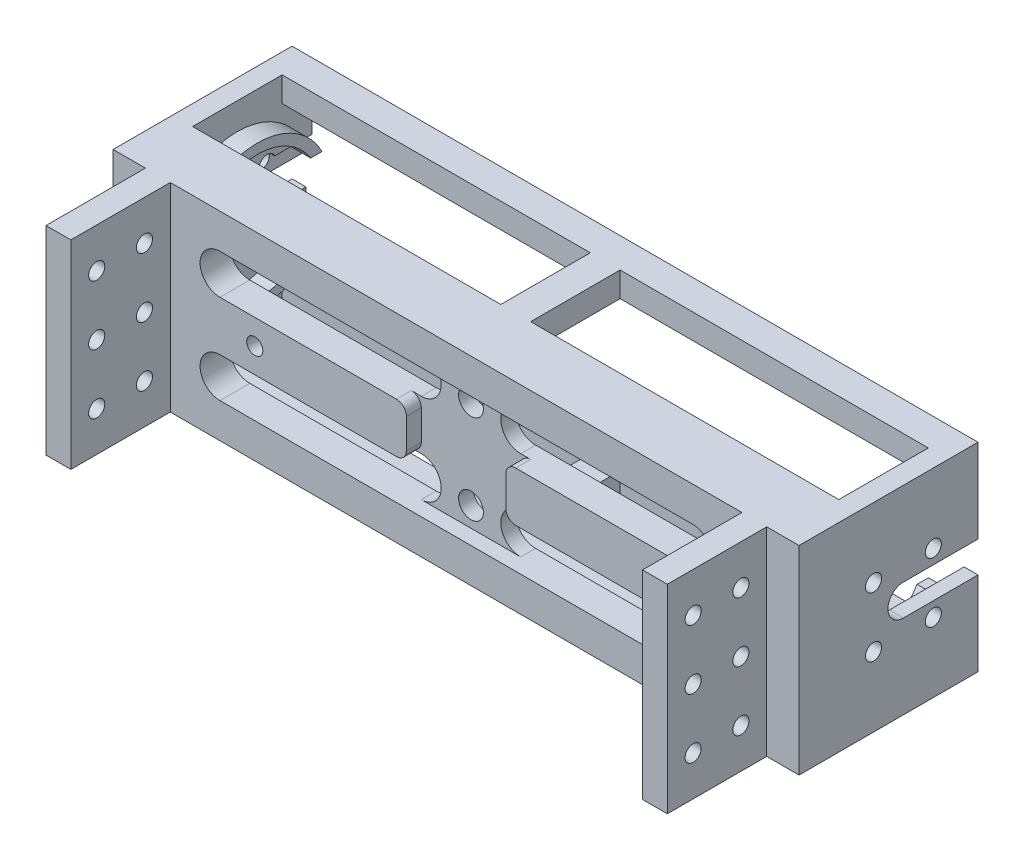
SolidWorks part; units mm, degrees
ref_plane "Plano frontal" through (0, 0, 0) normal (0, 0, 1) x (1, 0, 0)
ref_plane "Plano superior" through (0, 0, 0) normal (0, 1, 0) x (1, 0, 0)
ref_plane "Plano direito" through (0, 0, 0) normal (1, 0, 0) x (0, 0, -1)
sketch "Esboço1" plane through (0, 0, 0) normal (0, 0, 1) x (1, 0, 0)
  line L1 (32.5, -20) -> (-32.5, -20)
  line L2 (32.5, -20) -> (32.5, 20)
  line L3 (32.5, 20) -> (-32.5, 20)
  line L4 (-32.5, -20) -> (-32.5, 20)
  line L5 (32.5, -20) -> (-32.5, 20) construction
  line L6 (32.5, 20) -> (-32.5, -20) construction
  point P0 (0, 0)
  dimension "D1" = 65
  dimension "D2" = 40
extrude "Ressalto-extrusão1" add sketch "Esboço1" along normal blind 6
sketch "Esboço2" plane through (-32.5, 0, 0) normal (-1, 0, 0) x (0, 0, 1)
  line L0 (0, 20) -> (-30, 20)
  line L1 (-30, 20) -> (-30, -20)
  line L2 (-30, -20) -> (0, -20)
  line L4 (0, 20) -> (0, -20)
  line L5 (0, -20) -> (6, -20)
  line L6 (6, -20) -> (6, 20)
  line L7 (6, 20) -> (0, 20)
  line L8 (0, 20) -> (0, -20) construction
  line L9 (0, -20) -> (6, -20)
  line L10 (6, -20) -> (6, 20)
  line L11 (6, 20) -> (0, 20)
  dimension "D2" = 30
  dimension "D1" = 0
extrude "Ressalto-extrusão2" add sketch "Esboço2" along normal blind 4
sketch "Esboço3" plane through (-36.5, 0, 0) normal (-1, 0, 0) x (0, 0, 1)
  line L0 (0, 20) -> (0, -20) construction
  line L1 (0, 20) -> (0, -20) construction
  line L2 (-15, 3.125) -> (-30, 3.125)
  line L3 (0, 20) -> (-30, 20) construction
  line L4 (0, 20) -> (0, -20) construction
  line L5 (0, -20) -> (-30, -20) construction
  line L6 (-30, 20) -> (-30, -20) construction
  line L7 (-15, -20) -> (-15, 20) construction
  line L8 (0, 0) -> (-30, 0) construction
  line L9 (-30, 3.125) -> (-30, -3.125)
  line L10 (-30, -3.125) -> (-15, -3.125)
  arc A0 (-15, -3.125) -> (-15, 3.125) centre (-15, 0) ccw
  point P276 (-15, 0)
  dimension "D1" = 6.25
extrude "Corte-extrusão1" cut sketch "Esboço3" against normal through all
sketch "Esboço5" plane through (0, 0, 6) normal (0, 0, 1) x (1, 0, 0)
  line L0 (-36.5, -20) -> (32.5, -20) construction
  line L1 (-36.5, 20) -> (-30, 20)
  line L2 (-36.5, 20) -> (-36.5, -20)
  line L3 (-36.5, -20) -> (-30, -20)
  line L4 (-30, 20) -> (-30, -20)
  line L6 (-30, 20) -> (-25, 20)
  line L7 (-30, 20) -> (-30, -20)
  line L8 (-30, -20) -> (-25, -20)
  line L9 (-25, 20) -> (-25, -20)
  line L10 (-25, 20) -> (-21.5, 20)
  line L11 (-25, 20) -> (-25, -20)
  line L12 (-25, -20) -> (-21.5, -20)
  line L13 (-21.5, 20) -> (-21.5, -20)
  line M5 (32.5, 20) -> (-36.5, 20)
  line M7 (-36.5, -20) -> (32.5, -20)
  dimension "D1" = 15
  dimension "D2" = 6.5
  dimension "D3" = 5
extrude "Ressalto-extrusão4" add sketch "Esboço5" along normal blind 20 contours L9 L4 M5 M7 region at (-27.5, 0, 6)
sketch "Esboço7" plane through (-32.5, 0, 0) normal (1, 0, 0) x (0, 0, -1)
  line L0 (15, -6.625) -> (30, -6.625)
  line L1 (30, -3.125) -> (30, -20) construction
  line L2 (30, -6.625) -> (30, 6.625)
  line L3 (30, 20) -> (30, 3.125) construction
  line L4 (30, 6.625) -> (15, 6.625)
  arc A0 (15, 6.625) -> (15, -6.625) centre (15, 0) ccw
  dimension "D1" = 13.25
extrude "Corte-extrusão3" cut sketch "Esboço7" against normal blind 1.2
sketch "Esboço8" plane through (-32.5, 0, 0) normal (1, 0, 0) x (0, 0, -1)
  line L4 (15, -6.625) -> (30, -6.625) construction
  line L5 (25.7471, -6.625) -> (28.0384, -6.625)
  line L6 (30, 6.625) -> (15, 6.625) construction
  line L7 (28.0384, 6.625) -> (25.7471, 6.625)
  arc A0 (25.7471, 6.625) -> (25.7471, -6.625) centre (15, 0) ccw
  arc A1 (28.0384, 6.625) -> (28.0384, -6.625) centre (15, 0) ccw
  dimension "D1" = 25.25
extrude "Ressalto-extrusão5" add sketch "Esboço8" along normal blind 4
sketch "Esboço11" plane through (0, 0, 6) normal (0, 0, 1) x (1, 0, 0)
  line L0 (-15, 9) -> (22.5, 9) construction
  line L1 (-15, 13) -> (22.5, 13)
  line L2 (-15, 5) -> (22.5, 5)
  line L3 (-15, -9) -> (22.5, -9) construction
  line L4 (-15, -5) -> (22.5, -5)
  line L5 (-15, -13) -> (22.5, -13)
  line L6 (32.5, -20) -> (32.5, 20) construction
  line L7 (-25, 20) -> (-25, -20) construction
  line L8 (32.5, 20) -> (-25, 20) construction
  line L9 (-25, -20) -> (32.5, -20) construction
  line L10 (3.75, 20) -> (3.75, -20) construction
  arc A0 (-15, 13) -> (-15, 5) centre (-15, 9) ccw
  arc A1 (22.5, 5) -> (22.5, 13) centre (22.5, 9) ccw
  arc A2 (-15, -5) -> (-15, -13) centre (-15, -9) ccw
  arc A3 (22.5, -13) -> (22.5, -5) centre (22.5, -9) ccw
  point P2 (3.75, 9)
  point P7 (3.75, -9)
  dimension "D1" = 10
  dimension "D2" = 10
  dimension "D3" = 7
  dimension "D4" = 7
  dimension "D5" = 10
extrude "Corte-extrusão4" cut sketch "Esboço11" against normal through all
sketch "Esboço12" plane through (-32.5, 0, 0) normal (1, 0, 0) x (0, 0, -1)
  line L14 (0, -20) -> (6, -20)
  line L15 (0, -20) -> (0, -15)
  line L16 (0, -15) -> (6, -15)
  line L17 (6, -20) -> (6, -15)
  line L18 (30, -20) -> (24, -20)
  line L19 (30, -20) -> (30, -15)
  line L20 (30, -15) -> (24, -15)
  line L21 (24, -20) -> (24, -15)
  dimension "D1" = 5
  dimension "D3" = 6
extrude "Ressalto-extrusão6" add sketch "Esboço12" along normal up to surface (65 mm away) up to face at (32.5, 0, 3)
sketch "Esboço13" plane through (0, 0, -24) normal (0, 0, 1) x (1, 0, 0)
  line L0 (32.5, -15) -> (-32.5, -15) construction
  line L1 (32.5, -20) -> (29.5, -20)
  line L2 (32.5, -20) -> (32.5, -15)
  line L3 (32.5, -15) -> (29.5, -15)
  line L4 (29.5, -20) -> (29.5, -15)
  dimension "D1" = 3
extrude "Ressalto-extrusão7" add sketch "Esboço13" along normal up to surface (18 mm away) up to face at (0, -17.5, -6)
ref_plane "Plano1" through (0, 0, 0) normal (0, 1, 0) x (1, 0, 0)
sketch "Esboço14" plane through (0, 0, -24) normal (0, 0, 1) x (1, 0, 0)
  line L0 (29.5, -15) -> (-32.5, -15) construction
  line L1 (-4, -15) -> (1, -15)
  line L2 (-4, -15) -> (-4, -20)
  line L3 (-4, -20) -> (1, -20)
  line L4 (1, -15) -> (1, -20)
  line L5 (29.5, -20) -> (-32.5, -20) construction
  line L6 (-4, -17.5) -> (-32.5, -17.5) construction
  line L7 (-32.5, -15) -> (-32.5, -20) construction
  line L8 (1, -17.5) -> (29.5, -17.5) construction
  line L9 (29.5, -15) -> (29.5, -20) construction
mirror "Espelhar2" about plane through (0, 0, 0) normal (0, 1, 0) of "Ressalto-extrusão6", "Ressalto-extrusão7"
sketch "Esboço15" plane through (-30, 0, 0) normal (-1, 0, 0) x (0, 0, 1)
  line L0 (6, 0) -> (26, 0) construction
  line L1 (6, 20) -> (6, -20) construction
  line L2 (26, 20) -> (26, -20) construction
  line L3 (20.8, 20) -> (20.8, -20) construction
  line L4 (26, -20) -> (6, -20) construction
  line L5 (26, 20) -> (6, 20) construction
  line L6 (11.2, 20) -> (11.2, -20) construction
  line L7 (20.8, -12) -> (11.2, -12) construction
  line L8 (20.8, 12) -> (11.2, 12) construction
  circle A0 centre (20.8, 12) radius 1.625
  circle A1 centre (11.2, 12) radius 1.625
  circle A2 centre (20.8, 0) radius 1.625
  circle A3 centre (11.2, 0) radius 1.625
  circle A4 centre (20.8, -12) radius 1.625
  circle A5 centre (11.2, -12) radius 1.625
  dimension "D5" = 3.25
  dimension "D1" = 5.2
  dimension "D2" = 5.2
  dimension "D3" = 8
  dimension "D4" = 8
extrude "Corte-extrusão5" cut sketch "Esboço15" against normal up to surface (5 mm away) up to face at (-25, 0, 16)
ref_plane "Plano2" through (32.5, 0, 0) normal (1, 0, 0) x (0, 0, -1)
sketch "Esboço18" plane through (0, 0, 6) normal (0, 0, 1) x (1, 0, 0)
  line L0 (32.5, -20) -> (32.5, 20) construction
  line L1 (32.5, -20) -> (32.5, 20)
  line L2 (32.5, 0) -> (-25, 0) construction
  line L3 (-25, 20) -> (-25, -20) construction
  line L4 (-25, 20) -> (-25, -20)
  circle A0 centre (-8, 0) radius 1.625
  dimension "D2" = 3.25
  dimension "D1" = 40.5
extrude "Corte-extrusão6" cut sketch "Esboço18" against normal up to surface (6 mm away) contours A0 L2 | L2 A0 region at (-8, -0.6897, 6) region at (-8, 0.6897, 6) up to face at (3.75, -9, 0)
sketch "Esboço19" plane through (0, 0, 0) normal (0, 0, -1) x (-1, 0, 0)
  circle A0 centre (8, 0) radius 2.875
  dimension "D1" = 5.75
extrude "Corte-extrusão7" cut sketch "Esboço19" against normal blind 1.5
sketch "Esboço22" plane through (-36.5, 0, 0) normal (-1, 0, 0) x (0, 0, 1)
  line L0 (-8.9896, 6.0104) -> (-15, 0) construction
  line L1 (-15, 0) -> (-8.9896, 0) construction
  line L2 (-8.9896, 0) -> (-8.9896, 6.0104) construction
  circle A0 centre (-8.9896, 6.0104) radius 1.625
  circle A1 centre (-21.0104, 6.0104) radius 1.625
  circle A2 centre (-21.0104, -6.0104) radius 1.625
  circle A3 centre (-8.9896, -6.0104) radius 1.625
  point P15 (-15, 0)
  dimension "D3" = 3.25
  dimension "D1" = 8.5
  dimension "D2" = 45
  dimension "D4" = 4
extrude "Corte-extrusão10" cut sketch "Esboço22" against normal blind 4
mirror "Espelhar3" about plane through (32.5, 0, 0) normal (1, 0, 0) of bodies 121 115
sketch "Esboço20" plane through (0, 0, 6) normal (0, 0, 1) x (1, 0, 0)
  line L0 (42.5, -13) -> (22.5, -13)
  line L1 (22.5, -13) -> (22.5, -5)
  line L3 (42.5, -5) -> (42.5, -13)
  line L4 (42.5, 5) -> (42.5, 13)
  line L5 (42.5, 13) -> (22.5, 13)
  line L6 (22.5, 13) -> (22.5, 5)
  line L8 (42.5, 5) -> (42.5, -5)
  line L9 (22.5, -5) -> (22.5, 5)
  arc A0 (22.5, 5) -> (22.5, 13) centre (22.5, 9) ccw construction
extrude "Corte-extrusão8" cut sketch "Esboço20" against normal blind 3
sketch "Esboço21" plane through (0, 0, 3) normal (0, 0, 1) x (1, 0, 0)
  line L0 (26.5, 9) -> (38.5, 9) construction
  line L1 (26.5, -9) -> (38.5, -9) construction
  arc A0 (22.5, 5) -> (22.5, 13) centre (22.5, 9) ccw construction
  arc A1 (42.5, 13) -> (42.5, 5) centre (42.5, 9) ccw construction
  arc A2 (22.5, -13) -> (22.5, -5) centre (22.5, -9) ccw construction
  arc A3 (42.5, -5) -> (42.5, -13) centre (42.5, -9) ccw construction
  circle A4 centre (32.5, 9) radius 2.5
  circle A5 centre (32.5, -9) radius 2.5
  dimension "D1" = 5
extrude "Corte-extrusão9" cut sketch "Esboço21" against normal up to surface (3 mm away) up to face at (-10.875, 0, 0)
fillet "Filete1" radius 2 4 edges at (22.5, -5, 4.5) (22.5, 5, 4.5) (42.5, 5, 4.5) (42.5, -5, 4.5)
equation "\"3d\"= 0.25mm"
equation "\"D5@Esboço15\"= 3.00mm +\"3d\""
equation "\"D3@Esboço22\"=3.00mm +\"3d\""
equation "\"D2@Esboço18\"= 3.00mm +\"3d\""
equation "\"D1@Esboço3\"= 6.0mm + \"3d\""
equation "\"D1@Esboço7\"=13.00mm + \"3d\""
equation "\"D1@Esboço8\"= 25mm + \"3d\""
equation "\"D1@Esboço19\"= 5.5mm + \"3d\""
